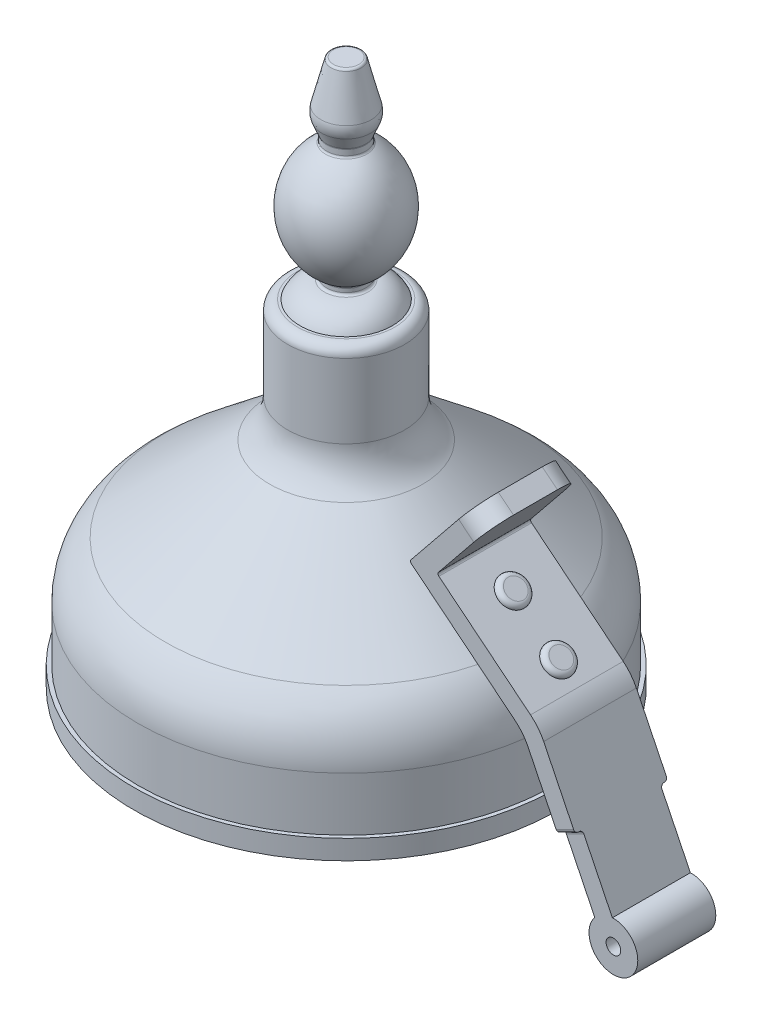
SolidWorks part; units mm, degrees
ref_plane "Front Plane" through (0, 0, 0) normal (0, 0, 1) x (1, 0, 0)
ref_plane "Top Plane" through (0, 0, 0) normal (0, 1, 0) x (1, 0, 0)
ref_plane "Right Plane" through (0, 0, 0) normal (1, 0, 0) x (0, 0, -1)
sketch "Sketch1" plane through (0, 0, 0) normal (0, 0, 1) x (1, 0, 0)
  line L0 (0, 0) -> (0, 120) construction
  line L1 (0, 0) -> (30, 0)
  line L2 (30, 0) -> (39, 8)
  line L3 (39, 8) -> (43.5, 8)
  line L4 (43.5, 8) -> (43.5, 12)
  line L5 (43.5, 12) -> (42.7, 12)
  line L6 (42.7, 12) -> (42.7, 23)
  line L7 (37.1338, 34.662) -> (15.7108, 51.9919)
  line L8 (12, 59.7666) -> (12, 74.951)
  line L9 (9.9573, 76.9937) -> (9.4572, 76.9937)
  line L10 (4, 81.7208) -> (4, 80.9807)
  line L11 (0, 120) -> (2.6114, 120)
  line L12 (3.0959, 119.6234) -> (5.175, 111.4585)
  line L13 (5.0031, 108.9624) -> (4.0369, 106.5907)
  line L14 (4, 106.4021) -> (4, 105.2792)
  line L15 (0, 0) -> (0, 120)
  arc A0 (42.7, 23) -> (37.1338, 34.662) centre (27.7, 23) ccw
  arc A1 (15.7108, 51.9919) -> (12, 59.7666) centre (22, 59.7666) cw
  arc A2 (4.4615, 80.4822) -> (9.4572, 76.9937) centre (4, 74.5) cw
  arc A3 (4.2334, 104.8562) -> (4.2334, 82.1438) centre (-2.9231, 93.5) cw
  arc A4 (5.175, 111.4585) -> (5.0031, 108.9624) centre (1.2987, 110.4715) cw
  arc A5 (4.0369, 106.5907) -> (4, 106.4021) centre (4.5, 106.4021) ccw
  arc A6 (2.6114, 120) -> (3.0959, 119.6234) centre (2.6114, 119.5) cw
  arc A7 (4, 105.2792) -> (4.2334, 104.8562) centre (4.5, 105.2792) ccw
  arc A8 (4, 80.9807) -> (4.4615, 80.4822) centre (4.5, 80.9807) ccw
  arc A9 (4.2334, 82.1438) -> (4, 81.7208) centre (4.5, 81.7208) ccw
  arc A10 (9.9573, 76.9937) -> (12, 74.951) centre (9.9573, 74.951) cw
  point P13 (12, 74.951)
  point P16 (12, 54.9937)
  point P22 (10.5, 93.5)
  point P29 (5.5, 110.1822)
  point P32 (4, 106.5)
  point P35 (3, 120)
  point P38 (4, 105)
  point P41 (4, 80.5)
  point P44 (4, 82)
  point P47 (12, 76.9937)
  dimension "D12" = 15
  dimension "D13" = 10
  dimension "D19" = 4
  dimension "D20" = 0.5
  dimension "D24" = 6
  dimension "D26" = 0.5
  dimension "D27" = 2.0427
  dimension "D1" = 120
  dimension "D2" = 30
  dimension "D3" = 8
  dimension "D4" = 39
  dimension "D5" = 43.5
  dimension "D6" = 4
  dimension "D7" = 0.8
  dimension "D8" = 11
  dimension "D9" = 0.5
  dimension "D10" = 22
  dimension "D11" = 12
  dimension "D14" = 3
  dimension "D15" = 15
  dimension "D16" = 1.5
  dimension "D17" = 5.5
  dimension "D18" = 4
  dimension "D21" = 23
  dimension "D22" = 21
  dimension "D23" = 1.5
  dimension "D25" = 6
revolve "Revolve1" add sketch "Sketch1" angle 360 about L0
sketch "Sketch2" plane through (0, 0, 0) normal (0, 0, 1) x (1, 0, 0)
  line L0 (22.4998, 46.5) -> (44.1003, 29.0266)
  line L1 (37.1338, 34.662) -> (15.7108, 51.9919) construction
  line L2 (46.7967, 25.6402) -> (58.9888, 0.6752)
  line L3 (22.4998, 46.5) -> (35.7072, 62.8268)
  line L4 (50.0019, 28.1924) -> (62.5831, 2.4306)
  line L5 (28.1254, 47.0942) -> (47.3054, 31.5788)
  line L6 (28.1254, 47.0942) -> (38.8171, 60.3111)
  line L7 (35.7072, 62.8268) -> (38.8171, 60.3111)
  line L8 (22.4998, 46.5) -> (45.8239, 27.6323) construction
  line L9 (45.8239, 27.6323) -> (58.9888, 0.6752) construction
  line L10 (49.029, 30.1845) -> (62.5831, 2.4306) construction
  line L11 (28.1254, 47.0942) -> (49.029, 30.1845) construction
  circle A0 centre (62.7969, -2.5649) radius 5
  circle A1 centre (62.7969, -2.5649) radius 1.5
  arc A2 (44.1003, 29.0266) -> (46.7967, 25.6402) centre (37.811, 21.2519) cw
  arc A3 (50.0019, 28.1924) -> (47.3054, 31.5788) centre (41.0162, 23.8041) ccw
  point P17 (45.8239, 27.6323)
  dimension "D7" = 10
  dimension "D8" = 3
  dimension "D9" = 10
  dimension "D1" = 21
  dimension "D2" = 30
  dimension "D3" = 30
  dimension "D4" = 155
  dimension "D5" = 46.5
  dimension "D6" = 4
extrude "Boss-Extrude1" add sketch "Sketch2" along normal mid plane 19 separate body contours L4 A3 L5 L6 L7 L3 L0 A2 L2 A0 | A0 A1
fillet "Fillet1" radius 5 2 edges at (37.2621, 61.569, -9.5) (37.2621, 61.569, 9.5)
fillet "Fillet2" radius 0.5 2 edges at (22.4998, 46.5, 0) (28.1254, 47.0942, 0)
sketch "Sketch3" plane through (34.1523, 42.2188, 0) normal (0.6289, 0.7775, 0) x (0.7775, -0.6289, 0)
  circle A0 centre (0, 0) radius 3
  circle A1 centre (12, 0) radius 3
  dimension "D1" = 6
  dimension "D2" = 12
extrude "Boss-Extrude2" add sketch "Sketch3" along normal blind 1
fillet "Fillet3" radius 1 2 edges at (32.4488, 44.883, 0) (41.7785, 37.336, 0)
sketch "Sketch4" plane through (51.4897, 25.1459, 0) normal (0.8986, 0.4388, 0) x (0, 0, -1)
  line L0 (-9.5, -34.862) -> (9.5, -34.862) construction
  line L1 (-8, -11.2794) -> (8, -11.2794)
  line L2 (-8, -11.2794) -> (-8, -34.862)
  line L3 (-8, -34.862) -> (8, -34.862)
  line L4 (8, -11.2794) -> (8, -34.862)
  line L5 (9.5, 3.3904) -> (9.5, -25.2794) construction
  line L6 (-9.5, 3.3904) -> (-9.5, -25.2794) construction
  line L7 (9.5, -11.2794) -> (9.5, -34.862)
  line L8 (9.5, -34.862) -> (9.5, -25.2794) construction
  line L9 (9.5, -34.862) -> (8, -34.862)
  line L10 (-8, -34.862) -> (-9.5, -34.862)
  line L11 (-9.5, -25.2794) -> (-9.5, -34.862) construction
  line L12 (-9.5, -34.862) -> (-9.5, -11.2794)
  line L13 (-9.5, -11.2794) -> (-8, -11.2794)
  line L14 (8, -11.2794) -> (9.5, -11.2794)
  point P15 (-9.5, -7.4792)
  point P20 (-9.5, -11.2752)
  point P21 (-9.5, -11.2752)
  line M5 (9.5, -25.2794) -> (9.5, 3.3904)
  line M7 (-9.5, 3.3904) -> (-9.5, -25.2794)
  line M8 (-9.5, -25.2794) -> (9.5, -25.2794)
  dimension "D1" = 1.5
  dimension "D2" = 1.5
  dimension "D3" = 14
extrude "Cut-Extrude1" cut sketch "Sketch4" against normal up to next and the other way up to next contours L13 L2 M7 M8 | L9 L7 L4 M8 | L14 L4 M8 M5 | L12 L10 L2 M8
fillet "Fillet4" radius 0.7 4 edges at (54.6423, 14.1329, -9.5) (54.6423, 14.1329, 9.5) (54.6423, 14.1329, 8) (54.6423, 14.1329, -8)
